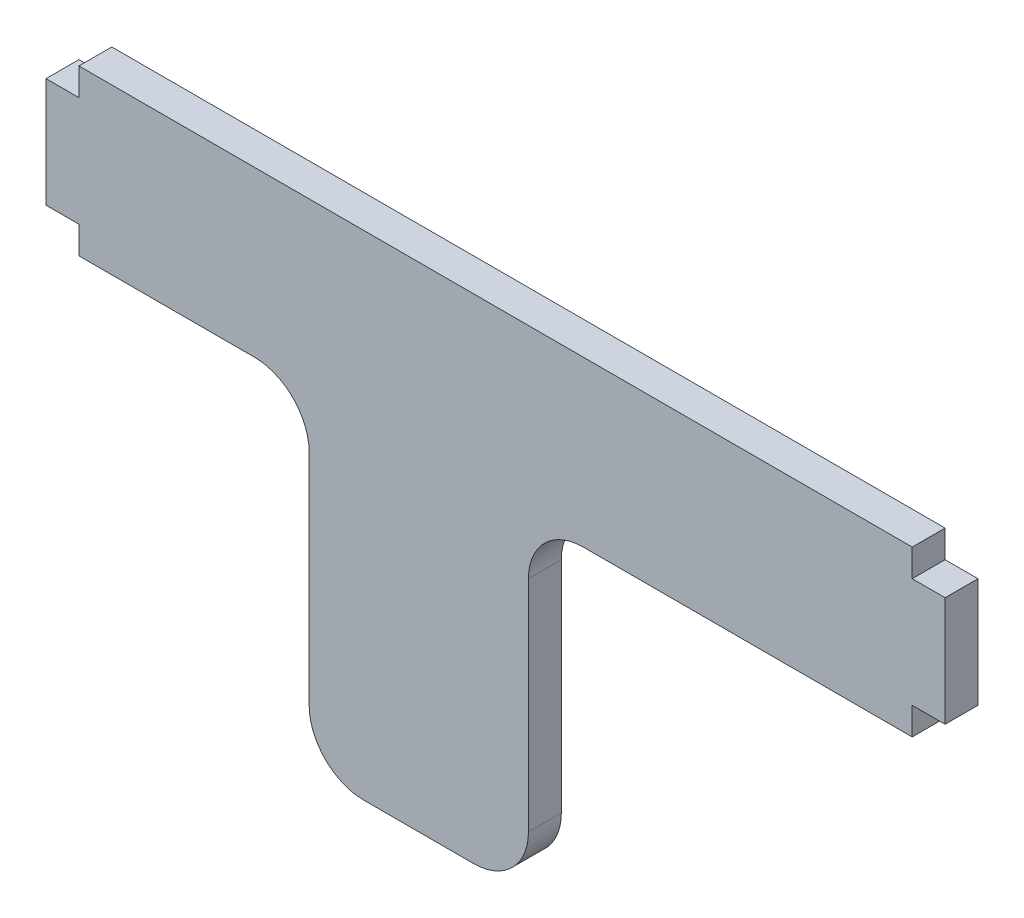
SolidWorks part; units mm, degrees
material "MDF"
ref_plane "Plano frontal" through (0, 0, 0) normal (0, 0, 1) x (1, 0, 0)
ref_plane "Plano superior" through (0, 0, 0) normal (0, 1, 0) x (1, 0, 0)
ref_plane "Plano direito" through (0, 0, 0) normal (1, 0, 0) x (0, 0, -1)
sketch "Esboço1" plane through (0, 0, 0) normal (0, 0, 1) x (1, 0, 0)
  line L0 (0, 0) -> (0, 7.5) construction
  line L1 (38, -7.5) -> (-38, -7.5)
  line L2 (38, -7.5) -> (38, 7.5)
  line L3 (38, 7.5) -> (-38, 7.5)
  line L4 (-38, -7.5) -> (-38, 7.5)
  line L5 (38, -7.5) -> (-38, 7.5) construction
  line L6 (38, 7.5) -> (-38, -7.5) construction
  line L7 (3, -37.5) -> (-17, -37.5)
  line L8 (3, -37.5) -> (3, -7.5)
  line L9 (3, -7.5) -> (-17, -7.5)
  line L10 (-17, -37.5) -> (-17, -7.5)
  line L11 (3, -37.5) -> (-17, -7.5) construction
  line L12 (3, -7.5) -> (-17, -37.5) construction
  line L13 (-41, -5) -> (-38, -5)
  line L14 (-41, -5) -> (-41, 5)
  line L15 (-41, 5) -> (-38, 5)
  line L16 (-38, -5) -> (-38, 5)
  line L17 (-41, -5) -> (-38, 5) construction
  line L18 (-41, 5) -> (-38, -5) construction
  line L19 (41, 5) -> (38, 5)
  line L20 (38, -5) -> (38, 5)
  line L21 (41, -5) -> (38, -5)
  line L22 (41, -5) -> (41, 5)
  point P0 (0, 0)
  point P6 (-7, -22.5)
  point P12 (-39.5, 0)
  dimension "D1" = 76
  dimension "D2" = 30
  dimension "D3" = 15
  dimension "D4" = 20
  dimension "D5" = 3
  dimension "D6" = 10
  dimension "D7" = 48
extrude "Ressalto-extrusão1" add sketch "Esboço1" along normal blind 3 contours L4 L1 L2 L3 | L10 L7 L8 L1 | L21 L22 L19 L2 | L15 L14 L13 L4 region at (0, 0, 0) region at (-7, -22.5, 0) region at (39.5, 0, 0) region at (-39.5, 0, 0)
fillet "Filete1" radius 5 4 edges at (3, -37.5, 1.5) (-17, -37.5, 1.5) (-17, -7.5, 1.5) (3, -7.5, 1.5)
